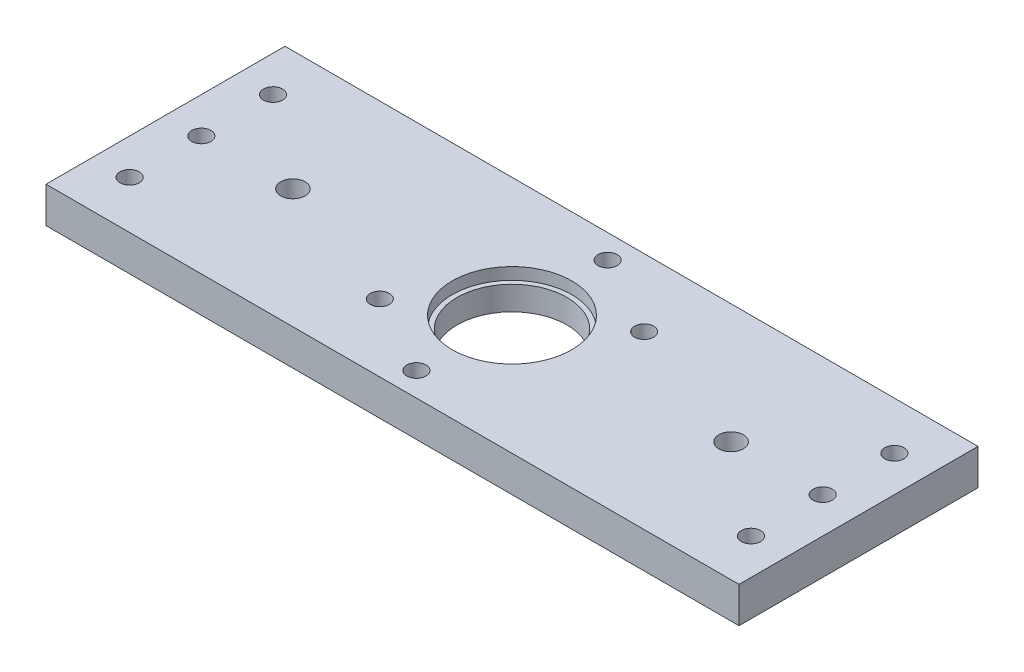
SolidWorks part; units mm, degrees
ref_plane "Front Plane" through (0, 0, 0) normal (0, 0, 1) x (1, 0, 0)
ref_plane "Top Plane" through (0, 0, 0) normal (0, 1, 0) x (1, 0, 0)
ref_plane "Right Plane" through (0, 0, 0) normal (1, 0, 0) x (0, 0, -1)
sketch "Sketch1" plane through (0, 0, 0) normal (0, 1, 0) x (1, 0, 0)
  line L1 (-92.075, -31.75) -> (92.075, -31.75)
  line L2 (-92.075, -31.75) -> (-92.075, 31.75)
  line L3 (-92.075, 31.75) -> (92.075, 31.75)
  line L4 (92.075, -31.75) -> (92.075, 31.75)
  line L5 (-92.075, -31.75) -> (92.075, 31.75) construction
  line L6 (-92.075, 31.75) -> (92.075, -31.75) construction
  point P0 (0, 0)
  dimension "D1" = 184.15
  dimension "D2" = 63.5
extrude "Boss-Extrude1" add sketch "Sketch1" along normal blind 9.525
sketch "Sketch2" plane through (0, 9.525, 0) normal (0, 1, 0) x (1, 0, 0)
  line L0 (-41.275, -31.75) -> (-41.275, 31.75)
  line L1 (-92.075, -31.75) -> (92.075, -31.75) construction
  line L2 (92.075, 31.75) -> (-92.075, 31.75) construction
  line L3 (-92.075, 31.75) -> (-92.075, -31.75) construction
  line L4 (41.275, 31.75) -> (41.275, -31.75)
  line L5 (92.075, -31.75) -> (92.075, 31.75) construction
  dimension "D1" = 50.8
  dimension "D2" = 50.8
sketch "Sketch3" plane through (0, 9.525, 0) normal (0, 1, 0) x (1, 0, 0)
  circle A0 centre (0, 0) radius 14.605
  dimension "D1" = 29.21
extrude "Cut-Extrude1" cut sketch "Sketch3" against normal through all
sketch "Sketch6" plane through (0, 0, 31.75) normal (0, 0, 1) x (1, 0, 0)
  line L0 (-41.275, 9.525) -> (-41.275, 0)
  line L1 (-92.075, 0) -> (92.075, 0) construction
sketch "Sketch7" plane through (0, 0, 0) normal (0, -1, 0) x (1, 0, 0)
  line L0 (-41.275, 31.75) -> (-41.275, -31.75)
  line L1 (92.075, -31.75) -> (-92.075, -31.75) construction
sketch "Sketch8" plane through (0, 0, 31.75) normal (0, 0, 1) x (1, 0, 0)
  line L0 (41.275, 9.525) -> (41.275, 0)
  line L1 (-92.075, 0) -> (92.075, 0) construction
  dimension "D1" = 82.55
  dimension "D2" = 82.55
sketch "Sketch9" plane through (0, 0, 0) normal (0, -1, 0) x (1, 0, 0)
  line L0 (41.275, 31.75) -> (41.275, -31.75)
  line L1 (92.075, -31.75) -> (-92.075, -31.75) construction
hole_wizard "#10 Clearance Hole1" positions "Sketch22" profile "Sketch23" hole size "#10" standard "ANSI Inch" end condition through all
sketch "Sketch22" plane through (0, 0, 0) normal (0, -1, 0) x (-1, 0, 0)
  point P0 (0, -25.4)
  point P2 (0, 25.4)
  dimension "D1" = 25.4
  dimension "D2" = 25.4
sketch "Sketch23" plane through (0, 0, 25.4) normal (1, 0, 0) x (0, 0, -1)
  line L0 (0, 0) -> (0, 9.525)
  line L1 (0, 9.525) -> (2.5527, 9.525)
  line L2 (2.5527, 9.525) -> (2.5527, 0)
  line L5 (2.5527, 0) -> (0, 0)
  line L11 (0, -6.35) -> (0, 107.95) construction
  dimension "Thru Hole Dia." = 5.1054
  dimension "Thru Hole Depth" = 9.525
hole_wizard "Ø6.5 (6.5) Diameter Hole3" positions "Sketch24" profile "Sketch25" hole size "Ø6.5" standard "ANSI Metric" end condition through all
sketch "Sketch24" plane through (0, 0, 0) normal (0, -1, 0) x (-1, 0, 0)
  line L0 (41.275, -31.75) -> (41.275, 31.75) construction
  line L1 (-41.275, 31.75) -> (-41.275, -31.75) construction
  point P0 (58.2083, 0)
  point P2 (-58.2083, 0)
  dimension "D1" = 16.9333
  dimension "D2" = 16.9333
sketch "Sketch25" plane through (-58.2083, 0, 0) normal (1, 0, 0) x (0, 0, -1)
  line L0 (0, 0) -> (0, 9.525)
  line L1 (0, 9.525) -> (3.25, 9.525)
  line L2 (3.25, 9.525) -> (3.25, 0)
  line L5 (3.25, 0) -> (0, 0)
  line L11 (0, -6.35) -> (0, 107.95) construction
  dimension "Thru Hole Dia." = 6.5
  dimension "Thru Hole Depth" = 9.525
sketch "Sketch29" plane through (0, 9.525, 0) normal (0, 1, 0) x (1, 0, 0)
  circle A0 centre (0, 0) radius 15.875
extrude "Cut-Extrude5" cut sketch "Sketch29" against normal blind 3.175
hole_wizard "#10 Clearance Hole2" positions "Sketch32" profile "Sketch31" hole size "#10" standard "ANSI Inch" end condition through all
sketch "Sketch32" plane through (0, 9.525, 0) normal (0, 1, 0) x (1, 0, 0)
  line L0 (92.075, 31.75) -> (-92.075, 31.75) construction
  line L1 (-92.075, 31.75) -> (-92.075, -31.75) construction
  line L2 (-92.075, -31.75) -> (92.075, -31.75) construction
  line L3 (92.075, -31.75) -> (92.075, 31.75) construction
  point P0 (-82.55, 19.05)
  point P2 (-82.55, -19.05)
  point P4 (82.55, -19.05)
  point P6 (82.55, 19.05)
  point P17 (-82.55, 0)
  point P19 (82.55, 0)
  dimension "D1" = 12.7
  dimension "D2" = 9.525
  dimension "D3" = 9.525
  dimension "D4" = 12.7
  dimension "D5" = 9.525
  dimension "D6" = 12.7
  dimension "D7" = 9.525
  dimension "D8" = 12.7
sketch "Sketch31" plane through (-82.55, 9.525, -19.05) normal (1, 0, 0) x (0, 0, 1)
  line L0 (0, 0) -> (0, 9.525)
  line L1 (0, 9.525) -> (2.5527, 9.525)
  line L2 (2.5527, 9.525) -> (2.5527, 0)
  line L5 (2.5527, 0) -> (0, 0)
  line L11 (0, -6.35) -> (0, 107.95) construction
  dimension "Thru Hole Dia." = 5.1054
  dimension "Thru Hole Depth" = 9.525
sketch "Sketch36" plane through (0, 0, 0) normal (0, -1, 0) x (1, 0, 0)
  line L0 (-92.075, 31.75) -> (92.075, 31.75) construction
  line L1 (92.075, -31.75) -> (-92.075, -31.75) construction
  circle A0 centre (-21.3292, 13.7922) radius 2.54
  circle A1 centre (21.3292, -13.7922) radius 2.54
  dimension "D1" = 25.4
  dimension "D2" = 5.08
  dimension "D4" = 5.08
  dimension "D3" = 17.9578
  dimension "D5" = 50.8
  dimension "D6" = 17.9578
extrude "Cut-Extrude6" cut sketch "Sketch36" against normal through all
